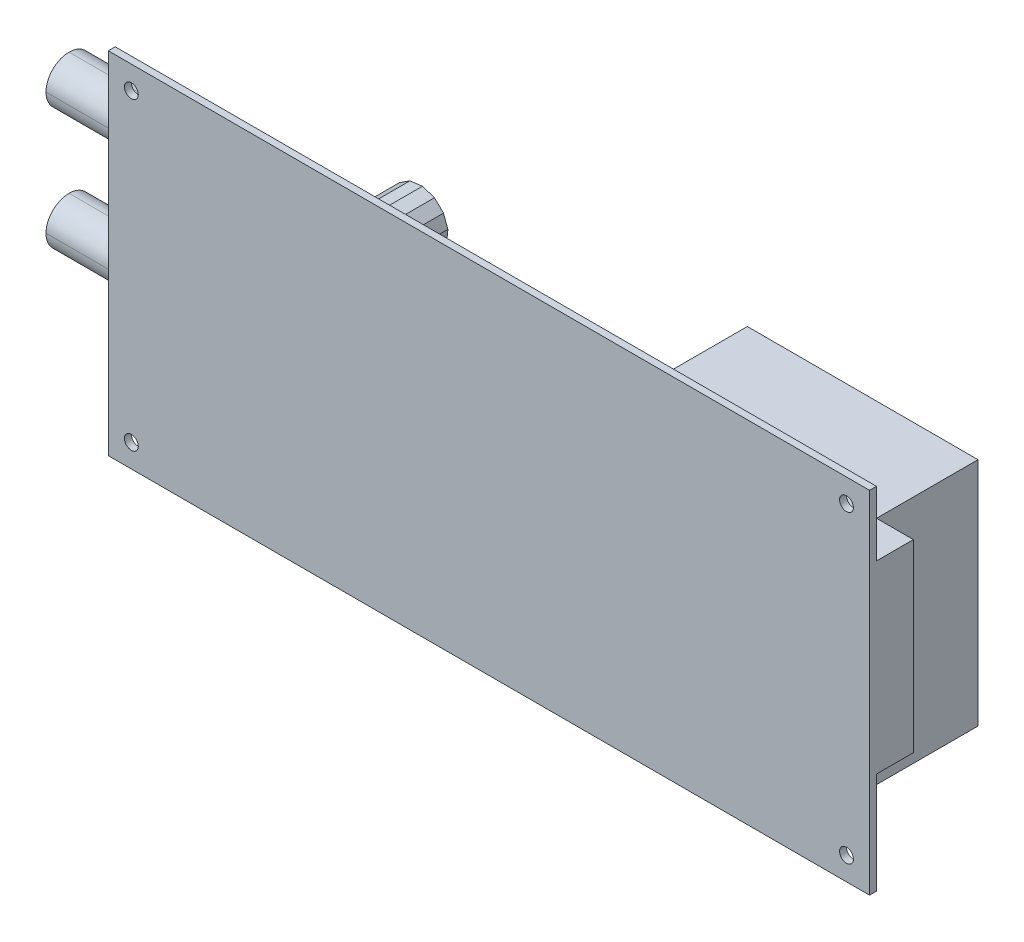
SolidWorks part; units mm, degrees
ref_plane "Front Plane" through (0, 0, 0) normal (0, 0, 1) x (1, 0, 0)
ref_plane "Top Plane" through (0, 0, 0) normal (0, 1, 0) x (1, 0, 0)
ref_plane "Right Plane" through (0, 0, 0) normal (1, 0, 0) x (0, 0, -1)
sketch "Sketch1" plane through (0, 0, 0) normal (0, 0, 1) x (1, 0, 0)
  line L1 (-35.2387, 26.9472) -> (129.7613, 26.9472)
  line L2 (-35.2387, 26.9472) -> (-35.2387, -49.0528)
  line L3 (-35.2387, -49.0528) -> (129.7613, -49.0528)
  line L4 (129.7613, 26.9472) -> (129.7613, -49.0528)
  dimension "D1" = 165
  dimension "D2" = 76
extrude "Boss-Extrude1" add sketch "Sketch1" along normal blind 1.5
sketch "Sketch2" plane through (0, 0, 1.5) normal (0, 0, 1) x (1, 0, 0)
  line L0 (129.7613, 26.9472) -> (-35.2387, 26.9472) construction
  line L1 (129.7613, -49.0528) -> (129.7613, 26.9472) construction
  line L2 (47.2613, 26.9472) -> (47.2613, -49.0528) construction
  line L3 (-35.2387, -49.0528) -> (129.7613, -49.0528) construction
  line L4 (-35.2387, -11.0528) -> (129.7613, -11.0528) construction
  line L5 (-35.2387, 26.9472) -> (-35.2387, -49.0528) construction
  circle A0 centre (124.7613, 21.9472) radius 1.5
  circle A1 centre (124.7613, -44.0528) radius 1.5
  circle A2 centre (-30.2387, -44.0528) radius 1.5
  circle A3 centre (-30.2387, 21.9472) radius 1.5
  dimension "D1" = 3
  dimension "D2" = 5
  dimension "D3" = 5
extrude "Cut-Extrude1" cut sketch "Sketch2" against normal up to next
sketch "Sketch3" plane through (0, 0, 0) normal (0, 0, -1) x (-1, 0, 0)
  line L0 (-129.7613, -49.0528) -> (-129.7613, 26.9472) construction
  line L1 (-129.7613, -27.0528) -> (-117.7613, -27.0528)
  line L2 (-129.7613, -27.0528) -> (-129.7613, 12.9472)
  line L3 (-129.7613, 12.9472) -> (-117.7613, 12.9472)
  line L4 (-117.7613, -27.0528) -> (-117.7613, 12.9472)
  line L5 (-129.7613, 26.9472) -> (35.2387, 26.9472) construction
  dimension "D1" = 12
  dimension "D2" = 40
  dimension "D3" = 14
extrude "Boss-Extrude2" add sketch "Sketch3" along normal blind 8
sketch "Sketch4" plane through (0, 0, 0) normal (0, 0, -1) x (-1, 0, 0)
  line L0 (35.2387, -49.0528) -> (-129.7613, -49.0528) construction
  line L1 (-69.7613, 10.9472) -> (-119.7613, 10.9472)
  line L2 (-69.7613, 10.9472) -> (-69.7613, -39.0528)
  line L3 (-69.7613, -39.0528) -> (-119.7613, -39.0528)
  line L4 (-119.7613, 10.9472) -> (-119.7613, -39.0528)
  line L5 (-129.7613, -49.0528) -> (-129.7613, -27.0528) construction
  dimension "D1" = 50
  dimension "D2" = 50
  dimension "D3" = 10
  dimension "D4" = 10
extrude "Boss-Extrude3" add sketch "Sketch4" along normal blind 32
sketch "Sketch5" plane through (0, 0, 0) normal (0, 0, -1) x (-1, 0, 0)
  line L0 (35.2387, 26.9472) -> (35.2387, -49.0528) construction
  line L1 (50.2387, 5.9472) -> (20.2387, 5.9472)
  line L2 (50.2387, 5.9472) -> (50.2387, 15.9472)
  line L3 (50.2387, 15.9472) -> (20.2387, 15.9472)
  line L4 (20.2387, 5.9472) -> (20.2387, 15.9472)
  line L5 (-129.7613, 26.9472) -> (35.2387, 26.9472) construction
  line L6 (20.2387, -20.5528) -> (50.2387, -20.5528)
  line L7 (20.2387, -20.5528) -> (20.2387, -10.5528)
  line L8 (20.2387, -10.5528) -> (50.2387, -10.5528)
  line L9 (50.2387, -20.5528) -> (50.2387, -10.5528)
  dimension "D1" = 15
  dimension "D2" = 10
  dimension "D3" = 30
  dimension "D4" = 26.5
  dimension "D5" = 11
extrude "Boss-Extrude4" add sketch "Sketch5" along normal blind 10
sketch "Sketch6" plane through (0, 0, 0) normal (0, 0, -1) x (-1, 0, 0)
  line L0 (-129.7613, 26.9472) -> (35.2387, 26.9472) construction
  line L2 (0.0792, 4.8874) -> (-1.341, 7.2294)
  line L3 (-10.1816, -1.3349) -> (-7.8859, -2.8287)
  line L4 (-7.8859, -2.8287) -> (-5.1694, -3.1785)
  line L5 (-5.1694, -3.1785) -> (-2.5701, -2.3151)
  line L6 (-2.5701, -2.3151) -> (-0.6029, -0.4093)
  line L7 (-0.6029, -0.4093) -> (0.3426, 2.1612)
  line L8 (0.3426, 2.1612) -> (0.0792, 4.8874)
  line L9 (-1.341, 7.2294) -> (-3.6367, 8.7232)
  line L10 (-3.6367, 8.7232) -> (-6.3532, 9.073)
  line L11 (-6.3532, 9.073) -> (-8.9525, 8.2095)
  line L12 (-8.9525, 8.2095) -> (-10.9197, 6.3038)
  line L13 (-10.9197, 6.3038) -> (-11.8652, 3.7333)
  line L14 (-11.8652, 3.7333) -> (-11.6018, 1.007)
  line L15 (-11.6018, 1.007) -> (-10.1816, -1.3349)
  line L16 (35.2387, 5.9472) -> (35.2387, -10.5528) construction
  circle A1 centre (-5.7613, 2.9472) radius 6 construction
  dimension "D1" = 41
  dimension "D4" = 12
  dimension "D5" = 24
extrude "Boss-Extrude5" add sketch "Sketch6" along normal blind 25
sketch "Sketch7" plane through (0, 0, 1.5) normal (0, 0, 1) x (1, 0, 0)
  line L0 (129.7613, -49.0528) -> (129.7613, 26.9472) construction
  line L1 (129.7613, -11.0528) -> (-35.2387, -11.0528) construction
  line L2 (-35.2387, 26.9472) -> (-35.2387, -49.0528) construction
  line L3 (47.2613, 26.9472) -> (47.2613, -49.0528) construction
  line L4 (129.7613, 26.9472) -> (-35.2387, 26.9472) construction
  line L5 (-35.2387, -49.0528) -> (129.7613, -49.0528) construction
  circle A0 centre (124.7613, 21.9472) radius 3
  circle A1 centre (124.7613, 21.9472) radius 1.5 construction
  circle A3 centre (124.7613, -44.0528) radius 3
  circle A4 centre (-30.2387, 21.9472) radius 3
  circle A5 centre (-30.2387, -44.0528) radius 3
  dimension "D1" = 6
extrude "Boss-Extrude6" [suppressed] add sketch "Sketch7" along normal blind 12
fillet "Fillet2" radius 5 8 edges at (-42.7387, 5.9472, 0) (-42.7387, 15.9472, 0) (-35.2387, 15.9472, -10) (-35.2387, 5.9472, -10) (-42.7387, -20.5528, 0) (-42.7387, -10.5528, 0) (-35.2387, -10.5528, -10) (-35.2387, -20.5528, -10)
sketch "Sketch8" plane through (-50.2387, 0, 0) normal (-1, 0, 0) x (0, 0, 1)
  circle A0 centre (-5, -15.5528) radius 4.5
  circle A1 centre (-5, 10.9472) radius 4.5
  arc A2 (-10, 10.9472) -> (-5, 5.9472) centre (-5, 10.9472) ccw construction
  arc A3 (-10, -15.5528) -> (-5, -20.5528) centre (-5, -15.5528) ccw construction
  circle A4 centre (-5, -15.5528) radius 0.75
  circle A5 centre (-5, 10.9472) radius 0.75
  dimension "D1" = 9
  dimension "D2" = 1.5
extrude "Cut-Extrude2" cut sketch "Sketch8" against normal blind 6
sketch "Sketch10" plane through (0, 0, -25) normal (0, 0, -1) x (-1, 0, 0)
  line L0 (-9.9361, 7.2567) -> (-1.5865, -1.3622) construction
  line L1 (-8.9525, 8.2095) -> (-10.9197, 6.3038) construction
  line L2 (-2.5701, -2.3151) -> (-0.6029, -0.4093) construction
  line L3 (-5.7613, 2.9472) -> (-1.341, 7.2294)
  line L4 (-1.341, 7.2294) -> (0.0792, 4.8874)
  line L5 (0.0792, 4.8874) -> (-5.7613, 2.9472)
  point P0 (-5.7613, 2.9472)
  point P4 (-5.7613, 2.9472)
extrude "Cut-Extrude3" cut sketch "Sketch10" against normal blind 3
